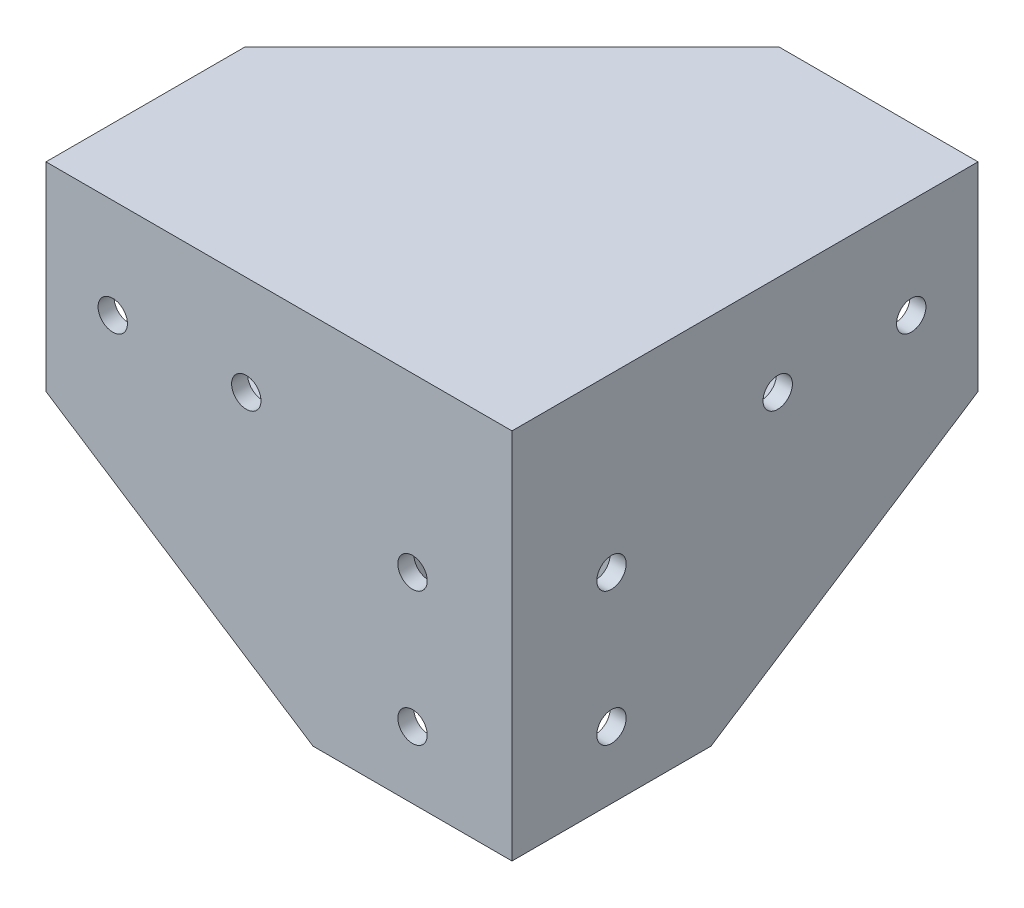
SolidWorks part; units mm, degrees
ref_plane "Front" through (0, 0, 0) normal (0, 0, 1) x (1, 0, 0)
ref_plane "Top" through (0, 0, 0) normal (0, 1, 0) x (1, 0, 0)
ref_plane "Right" through (0, 0, 0) normal (1, 0, 0) x (0, 0, -1)
sketch "Эскиз1" plane through (0, 0, 0) normal (0, 0, 1) x (1, 0, 0)
  line L1 (-12.5, -12.5) -> (12.5, -12.5)
  line L2 (-12.5, -12.5) -> (-12.5, 12.5)
  line L3 (-12.5, 12.5) -> (12.5, 12.5)
  line L4 (12.5, -12.5) -> (12.5, 12.5)
  line L5 (-12.5, -12.5) -> (12.5, 12.5) construction
  line L6 (-12.5, 12.5) -> (12.5, -12.5) construction
  point P0 (0, 0)
  dimension "D1" = 25
  dimension "D2" = 25
extrude "Вытянуть-Тонкостенный1" add sketch "Эскиз1" along normal blind 40 thin
sketch "Эскиз3" plane through (0, -14.9, 0) normal (0, -1, 0) x (1, 0, 0)
  line L0 (0, 40) -> (0, 78.0695) construction
  line L1 (-14.9, 40) -> (14.9, 40) construction
  line L3 (-12.5, 42.4) -> (12.5, 42.4)
  line L4 (-12.5, 42.4) -> (-12.5, 67.4)
  line L5 (-12.5, 67.4) -> (12.5, 67.4)
  line L6 (12.5, 42.4) -> (12.5, 67.4)
  line L7 (-12.5, 42.4) -> (12.5, 67.4) construction
  line L8 (-12.5, 67.4) -> (12.5, 42.4) construction
  point P5 (0, 54.9)
  dimension "D1" = 25
  dimension "D2" = 25
  dimension "D3" = 14.9
extrude "Вытянуть-Тонкостенный2" add sketch "Эскиз3" along normal blind 26 and the other way blind 29.8 thin
sketch "Эскиз4" plane through (0, 14.9, 0) normal (0, 1, 0) x (1, 0, 0)
  line L0 (-14.9, -69.8) -> (-14.9, 0) construction
  line L1 (14.9, -69.8) -> (-14.9, -69.8)
  line L2 (14.9, -69.8) -> (14.9, -40)
  line L3 (14.9, -40) -> (-14.9, -40)
  line L4 (-14.9, -69.8) -> (-14.9, -40)
  dimension "D1" = 29.8
extrude "Бобышка-Вытянуть1" add sketch "Эскиз4" against normal blind 2.4
sketch "Эскиз8" plane through (-14.9, 0, 0) normal (-1, 0, 0) x (0, 0, 1)
  line L0 (0, 0) -> (69.8, 0) construction
  line L1 (69.8, 14.9) -> (69.8, -40.9) construction
  line L2 (54.9, -40.9) -> (54.9, 0) construction
  line L3 (69.8, -40.9) -> (40, -40.9) construction
  line L5 (67.4, -12.5) -> (42.4, -12.5)
  line L6 (67.4, -12.5) -> (67.4, 12.5)
  line L7 (67.4, 12.5) -> (42.4, 12.5)
  line L8 (42.4, -12.5) -> (42.4, 12.5)
  line L9 (67.4, -12.5) -> (42.4, 12.5) construction
  line L10 (67.4, 12.5) -> (42.4, -12.5) construction
  dimension "D1" = 25
  dimension "D2" = 25
extrude "Вытянуть-Тонкостенный3" add sketch "Эскиз8" along normal blind 40 thin thin type one direction wall 2.4
fillet "Скругление1" radius 10 1 edges at (0, -14.9, 40)
fillet "Скругление2" radius 10 1 edges at (-14.9, 0, 40)
fillet "Скругление3" radius 10 3 edges at (-14.9, -17.8289, 37.0711) (-17.8289, -14.9, 37.0711) (-14.9, -14.9, 49.9)
sketch "Эскиз9" plane through (-14.9, 0, 0) normal (-1, 0, 0) x (0, 0, 1)
  circle A0 centre (15, 0) radius 2.2
  circle A1 centre (54.9, -29.9) radius 2.2
extrude "Вырез-Вытянуть1" cut sketch "Эскиз9" against normal up to next
sketch "Эскиз10" plane through (0, 0, 40) normal (0, 0, -1) x (-1, 0, 0)
  circle A0 centre (39.9, 0) radius 2.2
extrude "Вырез-Вытянуть2" cut sketch "Эскиз10" against normal up to next
sketch "Эскиз11" plane through (0, 0, 40) normal (0, 0, -1) x (-1, 0, 0)
  circle A0 centre (0, -29.9) radius 2.2
extrude "Вырез-Вытянуть3" cut sketch "Эскиз11" against normal up to next
sketch "Эскиз12" plane through (0, 0, 69.8) normal (0, 0, 1) x (1, 0, 0)
  line L0 (-54.9, 0) -> (0, 0) construction
  line L1 (-54.9, -14.9) -> (-54.9, 14.9) construction
  line L2 (0, 0) -> (0, -40.9) construction
  line L3 (14.9, -40.9) -> (-14.9, -40.9) construction
  circle A0 centre (-44.9, 0) radius 2.2
  circle A1 centre (-24.9, 0) radius 2.2
  circle A2 centre (0, -30.9) radius 2.2
  circle A3 centre (0, -10.9) radius 2.2
  dimension "D1" = 10
  dimension "D2" = 30
  dimension "D3" = 10
  dimension "D4" = 30
extrude "Вырез-Вытянуть4" cut sketch "Эскиз12" against normal up to next
sketch "Эскиз13" plane through (14.9, 0, 0) normal (1, 0, 0) x (0, 0, -1)
  line L0 (0, -14.9) -> (0, 14.9) construction
  line L1 (-40, -40.9) -> (-69.8, -40.9) construction
  circle A0 centre (-10, 0) radius 2.2
  circle A1 centre (-30, 0) radius 2.2
  circle A2 centre (-54.9, -30.9) radius 2.2
  circle A3 centre (-54.9, -10.9) radius 2.2
  dimension "D1" = 10
  dimension "D3" = 10
  dimension "D2" = 30
  dimension "D4" = 30
extrude "Вырез-Вытянуть5" cut sketch "Эскиз13" against normal up to next
sketch "Эскиз14" plane through (14.9, 0, 0) normal (1, 0, 0) x (0, 0, -1)
  line L0 (-40, -40.9) -> (0, -14.9)
  line L1 (0, -14.9) -> (-40, -14.9)
  line L2 (-40, -14.9) -> (-40, -40.9)
extrude "Бобышка-Вытянуть2" add sketch "Эскиз14" against normal blind 4
sketch "Эскиз15" plane through (0, 0, 69.8) normal (0, 0, 1) x (1, 0, 0)
  line L0 (-54.9, -14.9) -> (-14.9, -14.9)
  line L1 (-14.9, -14.9) -> (-14.9, -40.9)
  line L2 (-14.9, -40.9) -> (-54.9, -14.9)
extrude "Бобышка-Вытянуть3" add sketch "Эскиз15" against normal blind 4
sketch "Эскиз16" plane through (0, 14.9, 0) normal (0, 1, 0) x (1, 0, 0)
  line L0 (-54.9, -40) -> (-14.9, -40)
  line L1 (-14.9, -40) -> (-14.9, 0)
  line L2 (-14.9, 0) -> (-54.9, -40)
extrude "Бобышка-Вытянуть4" add sketch "Эскиз16" against normal blind 4
fillet "Скругление4" radius 4 9 edges at (10.9, -14.9, 15) (10.9, -17.8289, 37.0711) (-39.9, -14.9, 65.8) (-17.8289, -17.8289, 65.8) (10.9, -32.9, 40) (-14.9, -32.9, 65.8) (-39.9, 10.9, 40) (-17.8289, 10.9, 37.0711) (-14.9, 10.9, 15)
